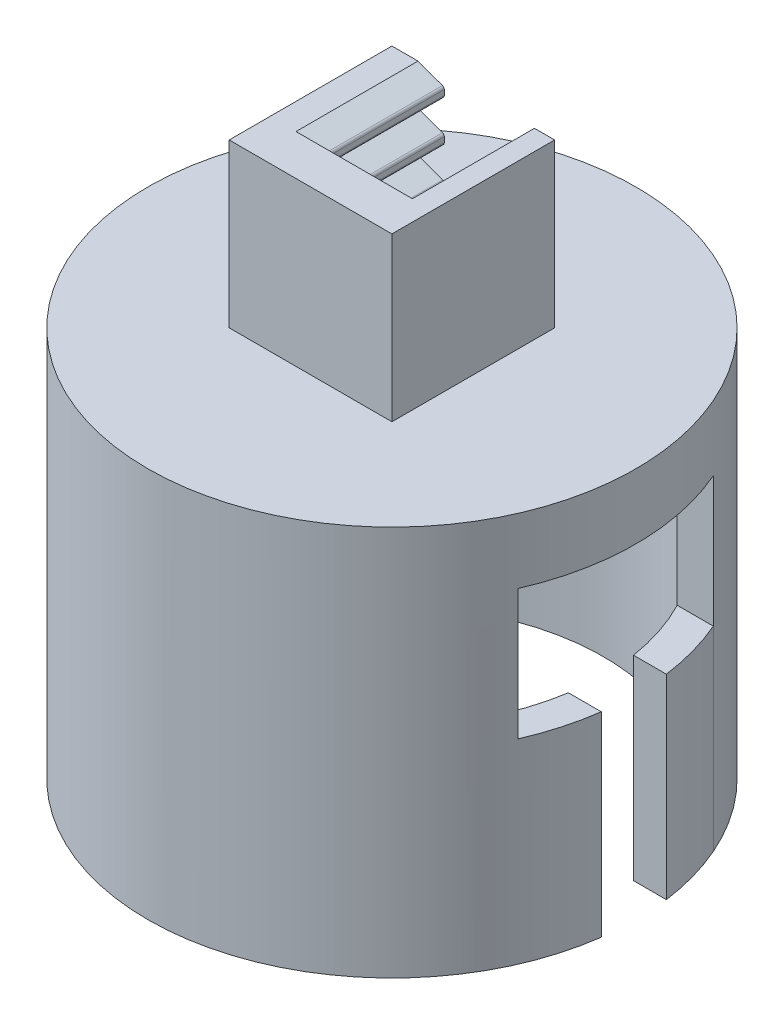
SolidWorks part; units mm, degrees
ref_plane "Front Plane" through (0, 0, 0) normal (0, 0, 1) x (1, 0, 0)
ref_plane "Top Plane" through (0, 0, 0) normal (0, 1, 0) x (1, 0, 0)
ref_plane "Right Plane" through (0, 0, 0) normal (1, 0, 0) x (0, 0, -1)
sketch "Sketch1" plane through (0, 0, 0) normal (0, 1, 0) x (1, 0, 0)
  circle A0 centre (0, 0) radius 15
  circle A1 centre (0, 0) radius 13
  dimension "D1" = 26
  dimension "D2" = 30
extrude "Boss-Extrude1" add sketch "Sketch1" along normal blind 20
sketch "Sketch2" plane through (0, 20, 0) normal (0, 1, 0) x (1, 0, 0)
  circle A0 centre (0, 0) radius 15
extrude "Boss-Extrude2" add sketch "Sketch2" along normal blind 4
ref_plane "Plane1" through (15, 0, 0) normal (1, 0, 0) x (0, 0, -1)
sketch "Sketch3" plane through (15, 0, 0) normal (1, 0, 0) x (0, 0, -1)
  line L0 (-15, 0) -> (15, 0) construction
  line L1 (-6, 12) -> (-2, 12)
  line L2 (-6, 12) -> (-6, 20)
  line L3 (-6, 20) -> (6, 20)
  line L4 (6, 12) -> (6, 20)
  line L5 (0, 24) -> (0, 0) construction
  line L6 (15, 24) -> (-15, 24) construction
  line L8 (-2, 12) -> (-2, 0)
  line L9 (-2, 0) -> (2, 0)
  line L10 (2, 12) -> (2, 0)
  line L11 (2, 12) -> (6, 12)
  dimension "D1" = 12
  dimension "D2" = 8
  dimension "D3" = 4
  dimension "D4" = 4
extrude "Cut-Extrude1" cut sketch "Sketch3" against normal blind 4
sketch "Sketch4" plane through (0, 24, 0) normal (0, 1, 0) x (1, 0, 0)
  line L0 (0, 5) -> (0, -5) construction
  line L1 (-5, 5) -> (5, 5)
  line L2 (-5, 5) -> (-5, -5)
  line L3 (-5, -5) -> (5, -5)
  line L4 (5, 5) -> (5, -5)
  line L5 (-5, 0) -> (5, 0) construction
  dimension "D1" = 10
  dimension "D2" = 10
extrude "Boss-Extrude3" add sketch "Sketch4" along normal blind 10
sketch "Sketch6" plane through (0, 0, -5) normal (0, 0, -1) x (-1, 0, 0)
  line L1 (-5, 34) -> (5, 34) construction
  line L3 (-3.7584, 34) -> (3.3958, 34)
  line L4 (-3.7584, 24) -> (3.5416, 24)
  line L405 (2.1355, 274) -> (0.2416, 274)
  line L406 (0.2416, 274) -> (0.2416, 34)
  line L407 (0.2416, 34) -> (-1.7584, 34)
  line L408 (-1.7584, 34) -> (-1.7584, 274)
  line L409 (-1.7584, 274) -> (-3.7584, 274)
  line L410 (-3.7584, 274) -> (-3.7584, 24)
  line L411 (-3.7584, 24) -> (3.5416, 24)
  line L412 (3.5416, 24) -> (3.5416, 24.6743)
  line L413 (3.5416, 24.6743) -> (1.8918, 25.2748)
  line L414 (1.7816, 25.432) -> (1.7816, 25.7555)
  line L415 (1.8918, 25.9128) -> (3.5416, 26.5133)
  line L416 (3.5416, 26.5133) -> (3.5416, 27.1876)
  line L417 (3.5416, 27.1876) -> (1.8918, 27.7881)
  line L418 (1.7816, 27.9453) -> (1.7816, 28.2688)
  line L419 (1.8918, 28.426) -> (3.5416, 29.0265)
  line L420 (3.5416, 29.0265) -> (3.5416, 29.7008)
  line L421 (3.5416, 29.7008) -> (1.8918, 30.3013)
  line L422 (1.7816, 30.4586) -> (1.7816, 30.7821)
  line L423 (1.8918, 30.9393) -> (3.5416, 31.5398)
  line L424 (3.5416, 31.5398) -> (3.5416, 32.2141)
  line L425 (3.5416, 32.2141) -> (1.8918, 32.8146)
  line L426 (1.7816, 32.9719) -> (1.7816, 33.2953)
  line L427 (1.8918, 33.4526) -> (3.5416, 34.0531)
  line L428 (3.5416, 34.0531) -> (3.5416, 34.7274)
  line L429 (3.5416, 34.7274) -> (1.8918, 35.3279)
  line L430 (1.7816, 35.4851) -> (1.7816, 35.8086)
  line L431 (1.8918, 35.9658) -> (3.5416, 36.5664)
  line L432 (3.5416, 36.5664) -> (3.5416, 37.2406)
  line L433 (3.5416, 37.2406) -> (1.8918, 37.8412)
  line L434 (1.7816, 37.9984) -> (1.7816, 38.3219)
  line L435 (1.8918, 38.4791) -> (3.5416, 39.0796)
  line L436 (3.5416, 39.0796) -> (3.5416, 39.7539)
  line L437 (3.5416, 39.7539) -> (1.8918, 40.3544)
  line L438 (1.7816, 40.5117) -> (1.7816, 40.8351)
  line L439 (1.8918, 40.9924) -> (3.5416, 41.5929)
  line L440 (3.5416, 41.5929) -> (3.5416, 42.2672)
  line L441 (3.5416, 42.2672) -> (1.8918, 42.8677)
  line L442 (1.7816, 43.025) -> (1.7816, 43.3484)
  line L443 (1.8918, 43.5057) -> (3.5416, 44.1062)
  line L444 (3.5416, 44.1062) -> (3.5416, 44.7805)
  line L445 (3.5416, 44.7805) -> (1.8918, 45.381)
  line L446 (1.7816, 45.5382) -> (1.7816, 45.8617)
  line L447 (1.8918, 46.0189) -> (3.5416, 46.6194)
  line L448 (3.5416, 46.6194) -> (3.5416, 47.2937)
  line L449 (3.5416, 47.2937) -> (1.8918, 47.8942)
  line L450 (1.7816, 48.0515) -> (1.7816, 48.375)
  line L451 (1.8918, 48.5322) -> (3.5416, 49.1327)
  line L452 (3.5416, 49.1327) -> (3.5416, 49.807)
  line L453 (3.5416, 49.807) -> (1.8918, 50.4075)
  line L454 (1.7816, 50.5648) -> (1.7816, 50.8882)
  line L455 (1.8918, 51.0455) -> (3.5416, 51.646)
  line L456 (3.5416, 51.646) -> (3.5416, 52.3203)
  line L457 (3.5416, 52.3203) -> (1.8918, 52.9208)
  line L458 (1.7816, 53.078) -> (1.7816, 53.4015)
  line L459 (1.8918, 53.5588) -> (3.5416, 54.1593)
  line L460 (3.5416, 54.1593) -> (3.5416, 54.8335)
  line L461 (3.5416, 54.8335) -> (1.8918, 55.4341)
  line L462 (1.7816, 55.5913) -> (1.7816, 55.9148)
  line L463 (1.8918, 56.072) -> (3.5416, 56.6725)
  line L464 (3.5416, 56.6725) -> (3.5416, 57.3468)
  line L465 (3.5416, 57.3468) -> (1.8918, 57.9473)
  line L466 (1.7816, 58.1046) -> (1.7816, 58.428)
  line L467 (1.8918, 58.5853) -> (3.5416, 59.1858)
  line L468 (3.5416, 59.1858) -> (3.5416, 59.8601)
  line L469 (3.5416, 59.8601) -> (1.8918, 60.4606)
  line L470 (1.7816, 60.6179) -> (1.7816, 60.9413)
  line L471 (1.8918, 61.0986) -> (3.5416, 61.6991)
  line L472 (3.5416, 61.6991) -> (3.5416, 62.3734)
  line L473 (3.5416, 62.3734) -> (1.8918, 62.9739)
  line L474 (1.7816, 63.1311) -> (1.7816, 63.4546)
  line L475 (1.8918, 63.6118) -> (3.5416, 64.2124)
  line L476 (3.5416, 64.2124) -> (3.5416, 64.8866)
  line L477 (3.5416, 64.8866) -> (1.8918, 65.4871)
  line L478 (1.7816, 65.6444) -> (1.7816, 65.9679)
  line L479 (1.8918, 66.1251) -> (3.5416, 66.7256)
  line L480 (3.5416, 66.7256) -> (3.5416, 67.3999)
  line L481 (3.5416, 67.3999) -> (1.8918, 68.0004)
  line L482 (1.7816, 68.1577) -> (1.7816, 68.4811)
  line L483 (1.8918, 68.6384) -> (3.5416, 69.2389)
  line L484 (3.5416, 69.2389) -> (3.5416, 69.9132)
  line L485 (3.5416, 69.9132) -> (1.8918, 70.5137)
  line L486 (1.7816, 70.6709) -> (1.7816, 70.9944)
  line L487 (1.8918, 71.1517) -> (3.5416, 71.7522)
  line L488 (3.5416, 71.7522) -> (3.5416, 72.4265)
  line L489 (3.5416, 72.4265) -> (1.8918, 73.027)
  line L490 (1.7816, 73.1842) -> (1.7816, 73.5077)
  line L491 (1.8918, 73.6649) -> (3.5416, 74.2654)
  line L492 (3.5416, 74.2654) -> (3.5416, 74.9397)
  line L493 (3.5416, 74.9397) -> (1.8918, 75.5402)
  line L494 (1.7816, 75.6975) -> (1.7816, 76.0209)
  line L495 (1.8918, 76.1782) -> (3.5416, 76.7787)
  line L496 (3.5416, 76.7787) -> (3.5416, 77.453)
  line L497 (3.5416, 77.453) -> (1.8918, 78.0535)
  line L498 (1.7816, 78.2108) -> (1.7816, 78.5342)
  line L499 (1.8918, 78.6915) -> (3.5416, 79.292)
  line L500 (3.5416, 79.292) -> (3.5416, 79.9663)
  line L501 (3.5416, 79.9663) -> (1.8918, 80.5668)
  line L502 (1.7816, 80.724) -> (1.7816, 81.0475)
  line L503 (1.8918, 81.2047) -> (3.5416, 81.8053)
  line L504 (3.5416, 81.8053) -> (3.5416, 82.4795)
  line L505 (3.5416, 82.4795) -> (1.8918, 83.0801)
  line L506 (1.7816, 83.2373) -> (1.7816, 83.5608)
  line L507 (1.8918, 83.718) -> (3.5416, 84.3185)
  line L508 (3.5416, 84.3185) -> (3.5416, 84.9928)
  line L509 (3.5416, 84.9928) -> (1.8918, 85.5933)
  line L510 (1.7816, 85.7506) -> (1.7816, 86.074)
  line L511 (1.8918, 86.2313) -> (3.5416, 86.8318)
  line L512 (3.5416, 86.8318) -> (3.5416, 87.5061)
  line L513 (3.5416, 87.5061) -> (1.8918, 88.1066)
  line L514 (1.7816, 88.2638) -> (1.7816, 88.5873)
  line L515 (1.8918, 88.7446) -> (3.5416, 89.3451)
  line L516 (3.5416, 89.3451) -> (3.5416, 90.0194)
  line L517 (3.5416, 90.0194) -> (1.8918, 90.6199)
  line L518 (1.7816, 90.7771) -> (1.7816, 91.1006)
  line L519 (1.8918, 91.2578) -> (3.5416, 91.8583)
  line L520 (3.5416, 91.8583) -> (3.5416, 92.5326)
  line L521 (3.5416, 92.5326) -> (1.8918, 93.1331)
  line L522 (1.7816, 93.2904) -> (1.7816, 93.6139)
  line L523 (1.8918, 93.7711) -> (3.5416, 94.3716)
  line L524 (3.5416, 94.3716) -> (3.5416, 95.0459)
  line L525 (3.5416, 95.0459) -> (1.8918, 95.6464)
  line L526 (1.7816, 95.8037) -> (1.7816, 96.1271)
  line L527 (1.8918, 96.2844) -> (3.5416, 96.8849)
  line L528 (3.5416, 96.8849) -> (3.5416, 97.5592)
  line L529 (3.5416, 97.5592) -> (1.8918, 98.1597)
  line L530 (1.7816, 98.3169) -> (1.7816, 98.6404)
  line L531 (1.8918, 98.7976) -> (3.5416, 99.3982)
  line L532 (3.5416, 99.3982) -> (3.5416, 100.0724)
  line L533 (3.5416, 100.0724) -> (1.8918, 100.673)
  line L534 (1.7816, 100.8302) -> (1.7816, 101.1537)
  line L535 (1.8918, 101.3109) -> (3.5416, 101.9114)
  line L536 (3.5416, 101.9114) -> (3.5416, 102.5857)
  line L537 (3.5416, 102.5857) -> (1.8918, 103.1862)
  line L538 (1.7816, 103.3435) -> (1.7816, 103.6669)
  line L539 (1.8918, 103.8242) -> (3.5416, 104.4247)
  line L540 (3.5416, 104.4247) -> (3.5416, 105.099)
  line L541 (3.5416, 105.099) -> (1.8918, 105.6995)
  line L542 (1.7816, 105.8568) -> (1.7816, 106.1802)
  line L543 (1.8918, 106.3375) -> (3.5416, 106.938)
  line L544 (3.5416, 106.938) -> (3.5416, 107.6123)
  line L545 (3.5416, 107.6123) -> (1.8918, 108.2128)
  line L546 (1.7816, 108.37) -> (1.7816, 108.6935)
  line L547 (1.8918, 108.8507) -> (3.5416, 109.4512)
  line L548 (3.5416, 109.4512) -> (3.5416, 110.1255)
  line L549 (3.5416, 110.1255) -> (1.8918, 110.726)
  line L550 (1.7816, 110.8833) -> (1.7816, 111.2068)
  line L551 (1.8918, 111.364) -> (3.5416, 111.9645)
  line L552 (3.5416, 111.9645) -> (3.5416, 112.6388)
  line L553 (3.5416, 112.6388) -> (1.8918, 113.2393)
  line L554 (1.7816, 113.3966) -> (1.7816, 113.72)
  line L555 (1.8918, 113.8773) -> (3.5416, 114.4778)
  line L556 (3.5416, 114.4778) -> (3.5416, 115.1521)
  line L557 (3.5416, 115.1521) -> (1.8918, 115.7526)
  line L558 (1.7816, 115.9098) -> (1.7816, 116.2333)
  line L559 (1.8918, 116.3906) -> (3.5416, 116.9911)
  line L560 (3.5416, 116.9911) -> (3.5416, 117.6653)
  line L561 (3.5416, 117.6653) -> (1.8918, 118.2659)
  line L562 (1.7816, 118.4231) -> (1.7816, 118.7466)
  line L563 (1.8918, 118.9038) -> (3.5416, 119.5043)
  line L564 (3.5416, 119.5043) -> (3.5416, 120.1786)
  line L565 (3.5416, 120.1786) -> (1.8918, 120.7791)
  line L566 (1.7816, 120.9364) -> (1.7816, 121.2598)
  line L567 (1.8918, 121.4171) -> (3.5416, 122.0176)
  line L568 (3.5416, 122.0176) -> (3.5416, 122.6919)
  line L569 (3.5416, 122.6919) -> (1.8918, 123.2924)
  line L570 (1.7816, 123.4497) -> (1.7816, 123.7731)
  line L571 (1.8918, 123.9304) -> (3.5416, 124.5309)
  line L572 (3.5416, 124.5309) -> (3.5416, 125.2052)
  line L573 (3.5416, 125.2052) -> (1.8918, 125.8057)
  line L574 (1.7816, 125.9629) -> (1.7816, 126.2864)
  line L575 (1.8918, 126.4436) -> (3.5416, 127.0442)
  line L576 (3.5416, 127.0442) -> (3.5416, 127.7184)
  line L577 (3.5416, 127.7184) -> (1.8918, 128.3189)
  line L578 (1.7816, 128.4762) -> (1.7816, 128.7997)
  line L579 (1.8918, 128.9569) -> (3.5416, 129.5574)
  line L580 (3.5416, 129.5574) -> (3.5416, 130.2317)
  line L581 (3.5416, 130.2317) -> (1.8918, 130.8322)
  line L582 (1.7816, 130.9895) -> (1.7816, 131.3129)
  line L583 (1.8918, 131.4702) -> (3.5416, 132.0707)
  line L584 (3.5416, 132.0707) -> (3.5416, 132.745)
  line L585 (3.5416, 132.745) -> (1.8918, 133.3455)
  line L586 (1.7816, 133.5027) -> (1.7816, 133.8262)
  line L587 (1.8918, 133.9835) -> (3.5416, 134.584)
  line L588 (3.5416, 134.584) -> (3.5416, 135.2583)
  line L589 (3.5416, 135.2583) -> (1.8918, 135.8588)
  line L590 (1.7816, 136.016) -> (1.7816, 136.3395)
  line L591 (1.8918, 136.4967) -> (3.5416, 137.0972)
  line L592 (3.5416, 137.0972) -> (3.5416, 137.7715)
  line L593 (3.5416, 137.7715) -> (1.8918, 138.372)
  line L594 (1.7816, 138.5293) -> (1.7816, 138.8527)
  line L595 (1.8918, 139.01) -> (3.5416, 139.6105)
  line L596 (3.5416, 139.6105) -> (3.5416, 140.2848)
  line L597 (3.5416, 140.2848) -> (1.8918, 140.8853)
  line L598 (1.7816, 141.0426) -> (1.7816, 141.366)
  line L599 (1.8918, 141.5233) -> (3.5416, 142.1238)
  line L600 (3.5416, 142.1238) -> (3.5416, 142.7981)
  line L601 (3.5416, 142.7981) -> (1.8918, 143.3986)
  line L602 (1.7816, 143.5558) -> (1.7816, 143.8793)
  line L603 (1.8918, 144.0365) -> (3.5416, 144.6371)
  line L604 (3.5416, 144.6371) -> (3.5416, 145.3113)
  line L605 (3.5416, 145.3113) -> (1.8918, 145.9119)
  line L606 (1.7816, 146.0691) -> (1.7816, 146.3926)
  line L607 (1.8918, 146.5498) -> (3.5416, 147.1503)
  line L608 (3.5416, 147.1503) -> (3.5416, 147.8246)
  line L609 (3.5416, 147.8246) -> (1.8918, 148.4251)
  line L610 (1.7816, 148.5824) -> (1.7816, 148.9058)
  line L611 (1.8918, 149.0631) -> (3.5416, 149.6636)
  line L612 (3.5416, 149.6636) -> (3.5416, 150.3379)
  line L613 (3.5416, 150.3379) -> (1.8918, 150.9384)
  line L614 (1.7816, 151.0956) -> (1.7816, 151.4191)
  line L615 (1.8918, 151.5764) -> (3.5416, 152.1769)
  line L616 (3.5416, 152.1769) -> (3.5416, 152.8512)
  line L617 (3.5416, 152.8512) -> (1.8918, 153.4517)
  line L618 (1.7816, 153.6089) -> (1.7816, 153.9324)
  line L619 (1.8918, 154.0896) -> (3.5416, 154.6901)
  line L620 (3.5416, 154.6901) -> (3.5416, 155.3644)
  line L621 (3.5416, 155.3644) -> (1.8918, 155.9649)
  line L622 (1.7816, 156.1222) -> (1.7816, 156.4457)
  line L623 (1.8918, 156.6029) -> (3.5416, 157.2034)
  line L624 (3.5416, 157.2034) -> (3.5416, 157.8777)
  line L625 (3.5416, 157.8777) -> (1.8918, 158.4782)
  line L626 (1.7816, 158.6355) -> (1.7816, 158.9589)
  line L627 (1.8918, 159.1162) -> (3.5416, 159.7167)
  line L628 (3.5416, 159.7167) -> (3.5416, 160.391)
  line L629 (3.5416, 160.391) -> (1.8918, 160.9915)
  line L630 (1.7816, 161.1487) -> (1.7816, 161.4722)
  line L631 (1.8918, 161.6294) -> (3.5416, 162.23)
  line L632 (3.5416, 162.23) -> (3.5416, 162.9042)
  line L633 (3.5416, 162.9042) -> (1.8918, 163.5048)
  line L634 (1.7816, 163.662) -> (1.7816, 163.9855)
  line L635 (1.8918, 164.1427) -> (3.5416, 164.7432)
  line L636 (3.5416, 164.7432) -> (3.5416, 165.4175)
  line L637 (3.5416, 165.4175) -> (1.8918, 166.018)
  line L638 (1.7816, 166.1753) -> (1.7816, 166.4987)
  line L639 (1.8918, 166.656) -> (3.5416, 167.2565)
  line L640 (3.5416, 167.2565) -> (3.5416, 167.9308)
  line L641 (3.5416, 167.9308) -> (1.8918, 168.5313)
  line L642 (1.7816, 168.6886) -> (1.7816, 169.012)
  line L643 (1.8918, 169.1693) -> (3.5416, 169.7698)
  line L644 (3.5416, 169.7698) -> (3.5416, 170.4441)
  line L645 (3.5416, 170.4441) -> (1.8918, 171.0446)
  line L646 (1.7816, 171.2018) -> (1.7816, 171.5253)
  line L647 (1.8918, 171.6825) -> (3.5416, 172.283)
  line L648 (3.5416, 172.283) -> (3.5416, 172.9573)
  line L649 (3.5416, 172.9573) -> (1.8918, 173.5578)
  line L650 (1.7816, 173.7151) -> (1.7816, 174.0386)
  line L651 (1.8918, 174.1958) -> (3.5416, 174.7963)
  line L652 (3.5416, 174.7963) -> (3.5416, 175.4706)
  line L653 (3.5416, 175.4706) -> (1.8918, 176.0711)
  line L654 (1.7816, 176.2284) -> (1.7816, 176.5518)
  line L655 (1.8918, 176.7091) -> (3.5416, 177.3096)
  line L656 (3.5416, 177.3096) -> (3.5416, 177.9839)
  line L657 (3.5416, 177.9839) -> (1.8918, 178.5844)
  line L658 (1.7816, 178.7416) -> (1.7816, 179.0651)
  line L659 (1.8918, 179.2224) -> (3.5416, 179.8229)
  line L660 (3.5416, 179.8229) -> (3.5416, 180.4971)
  line L661 (3.5416, 180.4971) -> (1.8918, 181.0977)
  line L662 (1.7816, 181.2549) -> (1.7816, 181.5784)
  line L663 (1.8918, 181.7356) -> (3.5416, 182.3361)
  line L664 (3.5416, 182.3361) -> (3.5416, 183.0104)
  line L665 (3.5416, 183.0104) -> (1.8918, 183.6109)
  line L666 (1.7816, 183.7682) -> (1.7816, 184.0916)
  line L667 (1.8918, 184.2489) -> (3.5416, 184.8494)
  line L668 (3.5416, 184.8494) -> (3.5416, 185.5237)
  line L669 (3.5416, 185.5237) -> (1.8918, 186.1242)
  line L670 (1.7816, 186.2815) -> (1.7816, 186.6049)
  line L671 (1.8918, 186.7622) -> (3.5416, 187.3627)
  line L672 (3.5416, 187.3627) -> (3.5416, 188.037)
  line L673 (3.5416, 188.037) -> (1.8918, 188.6375)
  line L674 (1.7816, 188.7947) -> (1.7816, 189.1182)
  line L675 (1.8918, 189.2754) -> (3.5416, 189.876)
  line L676 (3.5416, 189.876) -> (3.5416, 190.5502)
  line L677 (3.5416, 190.5502) -> (1.8918, 191.1507)
  line L678 (1.7816, 191.308) -> (1.7816, 191.6315)
  line L679 (1.8918, 191.7887) -> (3.5416, 192.3892)
  line L680 (3.5416, 192.3892) -> (3.5416, 193.0635)
  line L681 (3.5416, 193.0635) -> (1.8918, 193.664)
  line L682 (1.7816, 193.8213) -> (1.7816, 194.1447)
  line L683 (1.8918, 194.302) -> (3.5416, 194.9025)
  line L684 (3.5416, 194.9025) -> (3.5416, 195.5768)
  line L685 (3.5416, 195.5768) -> (1.8918, 196.1773)
  line L686 (1.7816, 196.3345) -> (1.7816, 196.658)
  line L687 (1.8918, 196.8153) -> (3.5416, 197.4158)
  line L688 (3.5416, 197.4158) -> (3.5416, 198.0901)
  line L689 (3.5416, 198.0901) -> (1.8918, 198.6906)
  line L690 (1.7816, 198.8478) -> (1.7816, 199.1713)
  line L691 (1.8918, 199.3285) -> (3.5416, 199.929)
  line L692 (3.5416, 199.929) -> (3.5416, 200.6033)
  line L693 (3.5416, 200.6033) -> (1.8918, 201.2038)
  line L694 (1.7816, 201.3611) -> (1.7816, 201.6845)
  line L695 (1.8918, 201.8418) -> (3.5416, 202.4423)
  line L696 (3.5416, 202.4423) -> (3.5416, 203.1166)
  line L697 (3.5416, 203.1166) -> (1.8918, 203.7171)
  line L698 (1.7816, 203.8744) -> (1.7816, 204.1978)
  line L699 (1.8918, 204.3551) -> (3.5416, 204.9556)
  line L700 (3.5416, 204.9556) -> (3.5416, 205.6299)
  line L701 (3.5416, 205.6299) -> (1.8918, 206.2304)
  line L702 (1.7816, 206.3876) -> (1.7816, 206.7111)
  line L703 (1.8918, 206.8683) -> (3.5416, 207.4689)
  line L704 (3.5416, 207.4689) -> (3.5416, 208.1431)
  line L705 (3.5416, 208.1431) -> (1.8918, 208.7437)
  line L706 (1.7816, 208.9009) -> (1.7816, 209.2244)
  line L707 (1.8918, 209.3816) -> (3.5416, 209.9821)
  line L708 (3.5416, 209.9821) -> (3.5416, 210.6564)
  line L709 (3.5416, 210.6564) -> (1.8918, 211.2569)
  line L710 (1.7816, 211.4142) -> (1.7816, 211.7376)
  line L711 (1.8918, 211.8949) -> (3.5416, 212.4954)
  line L712 (3.5416, 212.4954) -> (3.5416, 213.1697)
  line L713 (3.5416, 213.1697) -> (1.8918, 213.7702)
  line L714 (1.7816, 213.9274) -> (1.7816, 214.2509)
  line L715 (1.8918, 214.4082) -> (3.5416, 215.0087)
  line L716 (3.5416, 215.0087) -> (3.5416, 215.683)
  line L717 (3.5416, 215.683) -> (1.8918, 216.2835)
  line L718 (1.7816, 216.4407) -> (1.7816, 216.7642)
  line L719 (1.8918, 216.9214) -> (3.5416, 217.5219)
  line L720 (3.5416, 217.5219) -> (3.5416, 218.1962)
  line L721 (3.5416, 218.1962) -> (1.8918, 218.7967)
  line L722 (1.7816, 218.954) -> (1.7816, 219.2775)
  line L723 (1.8918, 219.4347) -> (3.5416, 220.0352)
  line L724 (3.5416, 220.0352) -> (3.5416, 220.7095)
  line L725 (3.5416, 220.7095) -> (1.8918, 221.31)
  line L726 (1.7816, 221.4673) -> (1.7816, 221.7907)
  line L727 (1.8918, 221.948) -> (3.5416, 222.5485)
  line L728 (3.5416, 222.5485) -> (3.5416, 223.2228)
  line L729 (3.5416, 223.2228) -> (1.8918, 223.8233)
  line L730 (1.7816, 223.9805) -> (1.7816, 224.304)
  line L731 (1.8918, 224.4612) -> (3.5416, 225.0618)
  line L732 (3.5416, 225.0618) -> (3.5416, 225.736)
  line L733 (3.5416, 225.736) -> (1.8918, 226.3366)
  line L734 (1.7816, 226.4938) -> (1.7816, 226.8173)
  line L735 (1.8918, 226.9745) -> (3.5416, 227.575)
  line L736 (3.5416, 227.575) -> (3.5416, 228.2493)
  line L737 (3.5416, 228.2493) -> (1.8918, 228.8498)
  line L738 (1.7816, 229.0071) -> (1.7816, 229.3305)
  line L739 (1.8918, 229.4878) -> (3.5416, 230.0883)
  line L740 (3.5416, 230.0883) -> (3.5416, 230.7626)
  line L741 (3.5416, 230.7626) -> (1.8918, 231.3631)
  line L742 (1.7816, 231.5204) -> (1.7816, 231.8438)
  line L743 (1.8918, 232.0011) -> (3.5416, 232.6016)
  line L744 (3.5416, 232.6016) -> (3.5416, 233.2759)
  line L745 (3.5416, 233.2759) -> (1.8918, 233.8764)
  line L746 (1.7816, 234.0336) -> (1.7816, 234.3571)
  line L747 (1.8918, 234.5143) -> (3.5416, 235.1148)
  line L748 (3.5416, 235.1148) -> (3.5416, 235.7891)
  line L749 (3.5416, 235.7891) -> (1.8918, 236.3896)
  line L750 (1.7816, 236.5469) -> (1.7816, 236.8704)
  line L751 (1.8918, 237.0276) -> (3.5416, 237.6281)
  line L752 (3.5416, 237.6281) -> (3.5416, 238.3024)
  line L753 (3.5416, 238.3024) -> (1.8918, 238.9029)
  line L754 (1.7816, 239.0602) -> (1.7816, 239.3836)
  line L755 (1.8918, 239.5409) -> (3.5416, 240.1414)
  line L756 (3.5416, 240.1414) -> (3.5416, 240.8157)
  line L757 (3.5416, 240.8157) -> (1.8918, 241.4162)
  line L758 (1.7816, 241.5734) -> (1.7816, 241.8969)
  line L759 (1.8918, 242.0542) -> (3.5416, 242.6547)
  line L760 (3.5416, 242.6547) -> (3.5416, 243.3289)
  line L761 (3.5416, 243.3289) -> (1.8918, 243.9295)
  line L762 (1.7816, 244.0867) -> (1.7816, 244.4102)
  line L763 (1.8918, 244.5674) -> (3.5416, 245.1679)
  line L764 (3.5416, 245.1679) -> (3.5416, 245.8422)
  line L765 (3.5416, 245.8422) -> (1.8918, 246.4427)
  line L766 (1.7816, 246.6) -> (1.7816, 246.9234)
  line L767 (1.8918, 247.0807) -> (3.5416, 247.6812)
  line L768 (3.5416, 247.6812) -> (3.5416, 248.3555)
  line L769 (3.5416, 248.3555) -> (1.8918, 248.956)
  line L770 (1.7816, 249.1133) -> (1.7816, 249.4367)
  line L771 (1.8918, 249.594) -> (3.5416, 250.1945)
  line L772 (3.5416, 250.1945) -> (3.5416, 250.8688)
  line L773 (3.5416, 250.8688) -> (1.8918, 251.4693)
  line L774 (1.7816, 251.6265) -> (1.7816, 251.95)
  line L775 (1.8918, 252.1072) -> (3.5416, 252.7078)
  line L776 (3.5416, 252.7078) -> (3.5416, 253.382)
  line L777 (3.5416, 253.382) -> (1.8918, 253.9825)
  line L778 (1.7816, 254.1398) -> (1.7816, 254.4633)
  line L779 (1.8918, 254.6205) -> (3.5416, 255.221)
  line L780 (3.5416, 255.221) -> (3.5416, 255.8953)
  line L781 (3.5416, 255.8953) -> (1.8918, 256.4958)
  line L782 (1.7816, 256.6531) -> (1.7816, 256.9765)
  line L783 (1.8918, 257.1338) -> (3.5416, 257.7343)
  line L784 (3.5416, 257.7343) -> (3.5416, 258.4086)
  line L785 (3.5416, 258.4086) -> (1.8918, 259.0091)
  line L786 (1.7816, 259.1663) -> (1.7816, 259.4898)
  line L787 (1.8918, 259.6471) -> (3.5416, 260.2476)
  line L788 (3.5416, 260.2476) -> (3.5416, 260.9219)
  line L789 (3.5416, 260.9219) -> (1.8918, 261.5224)
  line L790 (1.7816, 261.6796) -> (1.7816, 262.0031)
  line L791 (1.8918, 262.1603) -> (3.5416, 262.7608)
  line L792 (3.5416, 262.7608) -> (3.5416, 263.4351)
  line L793 (3.5416, 263.4351) -> (1.8918, 264.0356)
  line L794 (1.7816, 264.1929) -> (1.7816, 264.5163)
  line L795 (1.8918, 264.6736) -> (3.5416, 265.2741)
  line L796 (3.5416, 265.2741) -> (3.5416, 265.9484)
  line L797 (3.5416, 265.9484) -> (1.8918, 266.5489)
  line L798 (1.7816, 266.7062) -> (1.7816, 267.0296)
  line L799 (1.8918, 267.1869) -> (3.5416, 267.7874)
  line L800 (3.5416, 267.7874) -> (3.5416, 268.4617)
  line L801 (3.5416, 268.4617) -> (1.8918, 269.0622)
  line L802 (1.7816, 269.2194) -> (1.7816, 269.5429)
  line L803 (1.8918, 269.7001) -> (3.5416, 270.3007)
  line L804 (3.5416, 270.3007) -> (3.5416, 270.9749)
  line L805 (3.5416, 270.9749) -> (1.8918, 271.5755)
  line L806 (1.7816, 271.7327) -> (1.7816, 272.0562)
  line L807 (1.8918, 272.2134) -> (3.5416, 272.8139)
  line L808 (3.5416, 272.8139) -> (3.5416, 273.4882)
  line L809 (3.5416, 273.4882) -> (2.1355, 274)
  line L815 (-3.7584, 34) -> (-3.7584, 24)
  line L816 (-3.7584, 24) -> (3.5416, 24)
  line L817 (3.5416, 24) -> (3.5416, 24.6743)
  line L818 (3.5416, 24.6743) -> (1.8918, 25.2748)
  line L819 (1.7816, 25.432) -> (1.7816, 25.7555)
  line L820 (1.8918, 25.9128) -> (3.5416, 26.5133)
  line L821 (3.5416, 26.5133) -> (3.5416, 27.1876)
  line L822 (3.5416, 27.1876) -> (1.8918, 27.7881)
  line L823 (1.7816, 27.9453) -> (1.7816, 28.2688)
  line L824 (1.8918, 28.426) -> (3.5416, 29.0265)
  line L825 (3.5416, 29.0265) -> (3.5416, 29.7008)
  line L826 (3.5416, 29.7008) -> (1.8918, 30.3013)
  line L827 (1.7816, 30.4586) -> (1.7816, 30.7821)
  line L828 (1.8918, 30.9393) -> (3.5416, 31.5398)
  line L829 (3.5416, 31.5398) -> (3.5416, 32.2141)
  line L830 (3.5416, 32.2141) -> (1.8918, 32.8146)
  line L831 (1.7816, 32.9719) -> (1.7816, 33.2953)
  line L832 (1.8918, 33.4526) -> (3.3958, 34)
  arc A198 (1.7816, 25.432) -> (1.8918, 25.2748) centre (1.949, 25.432) ccw
  arc A199 (1.8918, 25.9128) -> (1.7816, 25.7555) centre (1.949, 25.7555) ccw
  arc A200 (1.7816, 27.9453) -> (1.8918, 27.7881) centre (1.949, 27.9453) ccw
  arc A201 (1.8918, 28.426) -> (1.7816, 28.2688) centre (1.949, 28.2688) ccw
  arc A202 (1.7816, 30.4586) -> (1.8918, 30.3013) centre (1.949, 30.4586) ccw
  arc A203 (1.8918, 30.9393) -> (1.7816, 30.7821) centre (1.949, 30.7821) ccw
  arc A204 (1.7816, 32.9719) -> (1.8918, 32.8146) centre (1.949, 32.9719) ccw
  arc A205 (1.8918, 33.4526) -> (1.7816, 33.2953) centre (1.949, 33.2953) ccw
  arc A206 (1.7816, 35.4851) -> (1.8918, 35.3279) centre (1.949, 35.4851) ccw
  arc A207 (1.8918, 35.9658) -> (1.7816, 35.8086) centre (1.949, 35.8086) ccw
  arc A208 (1.7816, 37.9984) -> (1.8918, 37.8412) centre (1.949, 37.9984) ccw
  arc A209 (1.8918, 38.4791) -> (1.7816, 38.3219) centre (1.949, 38.3219) ccw
  arc A210 (1.7816, 40.5117) -> (1.8918, 40.3544) centre (1.949, 40.5117) ccw
  arc A211 (1.8918, 40.9924) -> (1.7816, 40.8351) centre (1.949, 40.8351) ccw
  arc A212 (1.7816, 43.025) -> (1.8918, 42.8677) centre (1.949, 43.025) ccw
  arc A213 (1.8918, 43.5057) -> (1.7816, 43.3484) centre (1.949, 43.3484) ccw
  arc A214 (1.7816, 45.5382) -> (1.8918, 45.381) centre (1.949, 45.5382) ccw
  arc A215 (1.8918, 46.0189) -> (1.7816, 45.8617) centre (1.949, 45.8617) ccw
  arc A216 (1.7816, 48.0515) -> (1.8918, 47.8942) centre (1.949, 48.0515) ccw
  arc A217 (1.8918, 48.5322) -> (1.7816, 48.375) centre (1.949, 48.375) ccw
  arc A218 (1.7816, 50.5648) -> (1.8918, 50.4075) centre (1.949, 50.5648) ccw
  arc A219 (1.8918, 51.0455) -> (1.7816, 50.8882) centre (1.949, 50.8882) ccw
  arc A220 (1.7816, 53.078) -> (1.8918, 52.9208) centre (1.949, 53.078) ccw
  arc A221 (1.8918, 53.5588) -> (1.7816, 53.4015) centre (1.949, 53.4015) ccw
  arc A222 (1.7816, 55.5913) -> (1.8918, 55.4341) centre (1.949, 55.5913) ccw
  arc A223 (1.8918, 56.072) -> (1.7816, 55.9148) centre (1.949, 55.9148) ccw
  arc A224 (1.7816, 58.1046) -> (1.8918, 57.9473) centre (1.949, 58.1046) ccw
  arc A225 (1.8918, 58.5853) -> (1.7816, 58.428) centre (1.949, 58.428) ccw
  arc A226 (1.7816, 60.6179) -> (1.8918, 60.4606) centre (1.949, 60.6179) ccw
  arc A227 (1.8918, 61.0986) -> (1.7816, 60.9413) centre (1.949, 60.9413) ccw
  arc A228 (1.7816, 63.1311) -> (1.8918, 62.9739) centre (1.949, 63.1311) ccw
  arc A229 (1.8918, 63.6118) -> (1.7816, 63.4546) centre (1.949, 63.4546) ccw
  arc A230 (1.7816, 65.6444) -> (1.8918, 65.4871) centre (1.949, 65.6444) ccw
  arc A231 (1.8918, 66.1251) -> (1.7816, 65.9679) centre (1.949, 65.9679) ccw
  arc A232 (1.7816, 68.1577) -> (1.8918, 68.0004) centre (1.949, 68.1577) ccw
  arc A233 (1.8918, 68.6384) -> (1.7816, 68.4811) centre (1.949, 68.4811) ccw
  arc A234 (1.7816, 70.6709) -> (1.8918, 70.5137) centre (1.949, 70.6709) ccw
  arc A235 (1.8918, 71.1517) -> (1.7816, 70.9944) centre (1.949, 70.9944) ccw
  arc A236 (1.7816, 73.1842) -> (1.8918, 73.027) centre (1.949, 73.1842) ccw
  arc A237 (1.8918, 73.6649) -> (1.7816, 73.5077) centre (1.949, 73.5077) ccw
  arc A238 (1.7816, 75.6975) -> (1.8918, 75.5402) centre (1.949, 75.6975) ccw
  arc A239 (1.8918, 76.1782) -> (1.7816, 76.0209) centre (1.949, 76.0209) ccw
  arc A240 (1.7816, 78.2108) -> (1.8918, 78.0535) centre (1.949, 78.2108) ccw
  arc A241 (1.8918, 78.6915) -> (1.7816, 78.5342) centre (1.949, 78.5342) ccw
  arc A242 (1.7816, 80.724) -> (1.8918, 80.5668) centre (1.949, 80.724) ccw
  arc A243 (1.8918, 81.2047) -> (1.7816, 81.0475) centre (1.949, 81.0475) ccw
  arc A244 (1.7816, 83.2373) -> (1.8918, 83.0801) centre (1.949, 83.2373) ccw
  arc A245 (1.8918, 83.718) -> (1.7816, 83.5608) centre (1.949, 83.5608) ccw
  arc A246 (1.7816, 85.7506) -> (1.8918, 85.5933) centre (1.949, 85.7506) ccw
  arc A247 (1.8918, 86.2313) -> (1.7816, 86.074) centre (1.949, 86.074) ccw
  arc A248 (1.7816, 88.2638) -> (1.8918, 88.1066) centre (1.949, 88.2638) ccw
  arc A249 (1.8918, 88.7446) -> (1.7816, 88.5873) centre (1.949, 88.5873) ccw
  arc A250 (1.7816, 90.7771) -> (1.8918, 90.6199) centre (1.949, 90.7771) ccw
  arc A251 (1.8918, 91.2578) -> (1.7816, 91.1006) centre (1.949, 91.1006) ccw
  arc A252 (1.7816, 93.2904) -> (1.8918, 93.1331) centre (1.949, 93.2904) ccw
  arc A253 (1.8918, 93.7711) -> (1.7816, 93.6139) centre (1.949, 93.6139) ccw
  arc A254 (1.7816, 95.8037) -> (1.8918, 95.6464) centre (1.949, 95.8037) ccw
  arc A255 (1.8918, 96.2844) -> (1.7816, 96.1271) centre (1.949, 96.1271) ccw
  arc A256 (1.7816, 98.3169) -> (1.8918, 98.1597) centre (1.949, 98.3169) ccw
  arc A257 (1.8918, 98.7976) -> (1.7816, 98.6404) centre (1.949, 98.6404) ccw
  arc A258 (1.7816, 100.8302) -> (1.8918, 100.673) centre (1.949, 100.8302) ccw
  arc A259 (1.8918, 101.3109) -> (1.7816, 101.1537) centre (1.949, 101.1537) ccw
  arc A260 (1.7816, 103.3435) -> (1.8918, 103.1862) centre (1.949, 103.3435) ccw
  arc A261 (1.8918, 103.8242) -> (1.7816, 103.6669) centre (1.949, 103.6669) ccw
  arc A262 (1.7816, 105.8568) -> (1.8918, 105.6995) centre (1.949, 105.8568) ccw
  arc A263 (1.8918, 106.3375) -> (1.7816, 106.1802) centre (1.949, 106.1802) ccw
  arc A264 (1.7816, 108.37) -> (1.8918, 108.2128) centre (1.949, 108.37) ccw
  arc A265 (1.8918, 108.8507) -> (1.7816, 108.6935) centre (1.949, 108.6935) ccw
  arc A266 (1.7816, 110.8833) -> (1.8918, 110.726) centre (1.949, 110.8833) ccw
  arc A267 (1.8918, 111.364) -> (1.7816, 111.2068) centre (1.949, 111.2068) ccw
  arc A268 (1.7816, 113.3966) -> (1.8918, 113.2393) centre (1.949, 113.3966) ccw
  arc A269 (1.8918, 113.8773) -> (1.7816, 113.72) centre (1.949, 113.72) ccw
  arc A270 (1.7816, 115.9098) -> (1.8918, 115.7526) centre (1.949, 115.9098) ccw
  arc A271 (1.8918, 116.3906) -> (1.7816, 116.2333) centre (1.949, 116.2333) ccw
  arc A272 (1.7816, 118.4231) -> (1.8918, 118.2659) centre (1.949, 118.4231) ccw
  arc A273 (1.8918, 118.9038) -> (1.7816, 118.7466) centre (1.949, 118.7466) ccw
  arc A274 (1.7816, 120.9364) -> (1.8918, 120.7791) centre (1.949, 120.9364) ccw
  arc A275 (1.8918, 121.4171) -> (1.7816, 121.2598) centre (1.949, 121.2598) ccw
  arc A276 (1.7816, 123.4497) -> (1.8918, 123.2924) centre (1.949, 123.4497) ccw
  arc A277 (1.8918, 123.9304) -> (1.7816, 123.7731) centre (1.949, 123.7731) ccw
  arc A278 (1.7816, 125.9629) -> (1.8918, 125.8057) centre (1.949, 125.9629) ccw
  arc A279 (1.8918, 126.4436) -> (1.7816, 126.2864) centre (1.949, 126.2864) ccw
  arc A280 (1.7816, 128.4762) -> (1.8918, 128.3189) centre (1.949, 128.4762) ccw
  arc A281 (1.8918, 128.9569) -> (1.7816, 128.7997) centre (1.949, 128.7997) ccw
  arc A282 (1.7816, 130.9895) -> (1.8918, 130.8322) centre (1.949, 130.9895) ccw
  arc A283 (1.8918, 131.4702) -> (1.7816, 131.3129) centre (1.949, 131.3129) ccw
  arc A284 (1.7816, 133.5027) -> (1.8918, 133.3455) centre (1.949, 133.5027) ccw
  arc A285 (1.8918, 133.9835) -> (1.7816, 133.8262) centre (1.949, 133.8262) ccw
  arc A286 (1.7816, 136.016) -> (1.8918, 135.8588) centre (1.949, 136.016) ccw
  arc A287 (1.8918, 136.4967) -> (1.7816, 136.3395) centre (1.949, 136.3395) ccw
  arc A288 (1.7816, 138.5293) -> (1.8918, 138.372) centre (1.949, 138.5293) ccw
  arc A289 (1.8918, 139.01) -> (1.7816, 138.8527) centre (1.949, 138.8527) ccw
  arc A290 (1.7816, 141.0426) -> (1.8918, 140.8853) centre (1.949, 141.0426) ccw
  arc A291 (1.8918, 141.5233) -> (1.7816, 141.366) centre (1.949, 141.366) ccw
  arc A292 (1.7816, 143.5558) -> (1.8918, 143.3986) centre (1.949, 143.5558) ccw
  arc A293 (1.8918, 144.0365) -> (1.7816, 143.8793) centre (1.949, 143.8793) ccw
  arc A294 (1.7816, 146.0691) -> (1.8918, 145.9119) centre (1.949, 146.0691) ccw
  arc A295 (1.8918, 146.5498) -> (1.7816, 146.3926) centre (1.949, 146.3926) ccw
  arc A296 (1.7816, 148.5824) -> (1.8918, 148.4251) centre (1.949, 148.5824) ccw
  arc A297 (1.8918, 149.0631) -> (1.7816, 148.9058) centre (1.949, 148.9058) ccw
  arc A298 (1.7816, 151.0956) -> (1.8918, 150.9384) centre (1.949, 151.0956) ccw
  arc A299 (1.8918, 151.5764) -> (1.7816, 151.4191) centre (1.949, 151.4191) ccw
  arc A300 (1.7816, 153.6089) -> (1.8918, 153.4517) centre (1.949, 153.6089) ccw
  arc A301 (1.8918, 154.0896) -> (1.7816, 153.9324) centre (1.949, 153.9324) ccw
  arc A302 (1.7816, 156.1222) -> (1.8918, 155.9649) centre (1.949, 156.1222) ccw
  arc A303 (1.8918, 156.6029) -> (1.7816, 156.4457) centre (1.949, 156.4457) ccw
  arc A304 (1.7816, 158.6355) -> (1.8918, 158.4782) centre (1.949, 158.6355) ccw
  arc A305 (1.8918, 159.1162) -> (1.7816, 158.9589) centre (1.949, 158.9589) ccw
  arc A306 (1.7816, 161.1487) -> (1.8918, 160.9915) centre (1.949, 161.1487) ccw
  arc A307 (1.8918, 161.6294) -> (1.7816, 161.4722) centre (1.949, 161.4722) ccw
  arc A308 (1.7816, 163.662) -> (1.8918, 163.5048) centre (1.949, 163.662) ccw
  arc A309 (1.8918, 164.1427) -> (1.7816, 163.9855) centre (1.949, 163.9855) ccw
  arc A310 (1.7816, 166.1753) -> (1.8918, 166.018) centre (1.949, 166.1753) ccw
  arc A311 (1.8918, 166.656) -> (1.7816, 166.4987) centre (1.949, 166.4987) ccw
  arc A312 (1.7816, 168.6886) -> (1.8918, 168.5313) centre (1.949, 168.6886) ccw
  arc A313 (1.8918, 169.1693) -> (1.7816, 169.012) centre (1.949, 169.012) ccw
  arc A314 (1.7816, 171.2018) -> (1.8918, 171.0446) centre (1.949, 171.2018) ccw
  arc A315 (1.8918, 171.6825) -> (1.7816, 171.5253) centre (1.949, 171.5253) ccw
  arc A316 (1.7816, 173.7151) -> (1.8918, 173.5578) centre (1.949, 173.7151) ccw
  arc A317 (1.8918, 174.1958) -> (1.7816, 174.0386) centre (1.949, 174.0386) ccw
  arc A318 (1.7816, 176.2284) -> (1.8918, 176.0711) centre (1.949, 176.2284) ccw
  arc A319 (1.8918, 176.7091) -> (1.7816, 176.5518) centre (1.949, 176.5518) ccw
  arc A320 (1.7816, 178.7416) -> (1.8918, 178.5844) centre (1.949, 178.7416) ccw
  arc A321 (1.8918, 179.2224) -> (1.7816, 179.0651) centre (1.949, 179.0651) ccw
  arc A322 (1.7816, 181.2549) -> (1.8918, 181.0977) centre (1.949, 181.2549) ccw
  arc A323 (1.8918, 181.7356) -> (1.7816, 181.5784) centre (1.949, 181.5784) ccw
  arc A324 (1.7816, 183.7682) -> (1.8918, 183.6109) centre (1.949, 183.7682) ccw
  arc A325 (1.8918, 184.2489) -> (1.7816, 184.0916) centre (1.949, 184.0916) ccw
  arc A326 (1.7816, 186.2815) -> (1.8918, 186.1242) centre (1.949, 186.2815) ccw
  arc A327 (1.8918, 186.7622) -> (1.7816, 186.6049) centre (1.949, 186.6049) ccw
  arc A328 (1.7816, 188.7947) -> (1.8918, 188.6375) centre (1.949, 188.7947) ccw
  arc A329 (1.8918, 189.2754) -> (1.7816, 189.1182) centre (1.949, 189.1182) ccw
  arc A330 (1.7816, 191.308) -> (1.8918, 191.1507) centre (1.949, 191.308) ccw
  arc A331 (1.8918, 191.7887) -> (1.7816, 191.6315) centre (1.949, 191.6315) ccw
  arc A332 (1.7816, 193.8213) -> (1.8918, 193.664) centre (1.949, 193.8213) ccw
  arc A333 (1.8918, 194.302) -> (1.7816, 194.1447) centre (1.949, 194.1447) ccw
  arc A334 (1.7816, 196.3345) -> (1.8918, 196.1773) centre (1.949, 196.3345) ccw
  arc A335 (1.8918, 196.8153) -> (1.7816, 196.658) centre (1.949, 196.658) ccw
  arc A336 (1.7816, 198.8478) -> (1.8918, 198.6906) centre (1.949, 198.8478) ccw
  arc A337 (1.8918, 199.3285) -> (1.7816, 199.1713) centre (1.949, 199.1713) ccw
  arc A338 (1.7816, 201.3611) -> (1.8918, 201.2038) centre (1.949, 201.3611) ccw
  arc A339 (1.8918, 201.8418) -> (1.7816, 201.6845) centre (1.949, 201.6845) ccw
  arc A340 (1.7816, 203.8744) -> (1.8918, 203.7171) centre (1.949, 203.8744) ccw
  arc A341 (1.8918, 204.3551) -> (1.7816, 204.1978) centre (1.949, 204.1978) ccw
  arc A342 (1.7816, 206.3876) -> (1.8918, 206.2304) centre (1.949, 206.3876) ccw
  arc A343 (1.8918, 206.8683) -> (1.7816, 206.7111) centre (1.949, 206.7111) ccw
  arc A344 (1.7816, 208.9009) -> (1.8918, 208.7437) centre (1.949, 208.9009) ccw
  arc A345 (1.8918, 209.3816) -> (1.7816, 209.2244) centre (1.949, 209.2244) ccw
  arc A346 (1.7816, 211.4142) -> (1.8918, 211.2569) centre (1.949, 211.4142) ccw
  arc A347 (1.8918, 211.8949) -> (1.7816, 211.7376) centre (1.949, 211.7376) ccw
  arc A348 (1.7816, 213.9274) -> (1.8918, 213.7702) centre (1.949, 213.9274) ccw
  arc A349 (1.8918, 214.4082) -> (1.7816, 214.2509) centre (1.949, 214.2509) ccw
  arc A350 (1.7816, 216.4407) -> (1.8918, 216.2835) centre (1.949, 216.4407) ccw
  arc A351 (1.8918, 216.9214) -> (1.7816, 216.7642) centre (1.949, 216.7642) ccw
  arc A352 (1.7816, 218.954) -> (1.8918, 218.7967) centre (1.949, 218.954) ccw
  arc A353 (1.8918, 219.4347) -> (1.7816, 219.2775) centre (1.949, 219.2775) ccw
  arc A354 (1.7816, 221.4673) -> (1.8918, 221.31) centre (1.949, 221.4673) ccw
  arc A355 (1.8918, 221.948) -> (1.7816, 221.7907) centre (1.949, 221.7907) ccw
  arc A356 (1.7816, 223.9805) -> (1.8918, 223.8233) centre (1.949, 223.9805) ccw
  arc A357 (1.8918, 224.4612) -> (1.7816, 224.304) centre (1.949, 224.304) ccw
  arc A358 (1.7816, 226.4938) -> (1.8918, 226.3366) centre (1.949, 226.4938) ccw
  arc A359 (1.8918, 226.9745) -> (1.7816, 226.8173) centre (1.949, 226.8173) ccw
  arc A360 (1.7816, 229.0071) -> (1.8918, 228.8498) centre (1.949, 229.0071) ccw
  arc A361 (1.8918, 229.4878) -> (1.7816, 229.3305) centre (1.949, 229.3305) ccw
  arc A362 (1.7816, 231.5204) -> (1.8918, 231.3631) centre (1.949, 231.5204) ccw
  arc A363 (1.8918, 232.0011) -> (1.7816, 231.8438) centre (1.949, 231.8438) ccw
  arc A364 (1.7816, 234.0336) -> (1.8918, 233.8764) centre (1.949, 234.0336) ccw
  arc A365 (1.8918, 234.5143) -> (1.7816, 234.3571) centre (1.949, 234.3571) ccw
  arc A366 (1.7816, 236.5469) -> (1.8918, 236.3896) centre (1.949, 236.5469) ccw
  arc A367 (1.8918, 237.0276) -> (1.7816, 236.8704) centre (1.949, 236.8704) ccw
  arc A368 (1.7816, 239.0602) -> (1.8918, 238.9029) centre (1.949, 239.0602) ccw
  arc A369 (1.8918, 239.5409) -> (1.7816, 239.3836) centre (1.949, 239.3836) ccw
  arc A370 (1.7816, 241.5734) -> (1.8918, 241.4162) centre (1.949, 241.5734) ccw
  arc A371 (1.8918, 242.0542) -> (1.7816, 241.8969) centre (1.949, 241.8969) ccw
  arc A372 (1.7816, 244.0867) -> (1.8918, 243.9295) centre (1.949, 244.0867) ccw
  arc A373 (1.8918, 244.5674) -> (1.7816, 244.4102) centre (1.949, 244.4102) ccw
  arc A374 (1.7816, 246.6) -> (1.8918, 246.4427) centre (1.949, 246.6) ccw
  arc A375 (1.8918, 247.0807) -> (1.7816, 246.9234) centre (1.949, 246.9234) ccw
  arc A376 (1.7816, 249.1133) -> (1.8918, 248.956) centre (1.949, 249.1133) ccw
  arc A377 (1.8918, 249.594) -> (1.7816, 249.4367) centre (1.949, 249.4367) ccw
  arc A378 (1.7816, 251.6265) -> (1.8918, 251.4693) centre (1.949, 251.6265) ccw
  arc A379 (1.8918, 252.1072) -> (1.7816, 251.95) centre (1.949, 251.95) ccw
  arc A380 (1.7816, 254.1398) -> (1.8918, 253.9825) centre (1.949, 254.1398) ccw
  arc A381 (1.8918, 254.6205) -> (1.7816, 254.4633) centre (1.949, 254.4633) ccw
  arc A382 (1.7816, 256.6531) -> (1.8918, 256.4958) centre (1.949, 256.6531) ccw
  arc A383 (1.8918, 257.1338) -> (1.7816, 256.9765) centre (1.949, 256.9765) ccw
  arc A384 (1.7816, 259.1663) -> (1.8918, 259.0091) centre (1.949, 259.1663) ccw
  arc A385 (1.8918, 259.6471) -> (1.7816, 259.4898) centre (1.949, 259.4898) ccw
  arc A386 (1.7816, 261.6796) -> (1.8918, 261.5224) centre (1.949, 261.6796) ccw
  arc A387 (1.8918, 262.1603) -> (1.7816, 262.0031) centre (1.949, 262.0031) ccw
  arc A388 (1.7816, 264.1929) -> (1.8918, 264.0356) centre (1.949, 264.1929) ccw
  arc A389 (1.8918, 264.6736) -> (1.7816, 264.5163) centre (1.949, 264.5163) ccw
  arc A390 (1.7816, 266.7062) -> (1.8918, 266.5489) centre (1.949, 266.7062) ccw
  arc A391 (1.8918, 267.1869) -> (1.7816, 267.0296) centre (1.949, 267.0296) ccw
  arc A392 (1.7816, 269.2194) -> (1.8918, 269.0622) centre (1.949, 269.2194) ccw
  arc A393 (1.8918, 269.7001) -> (1.7816, 269.5429) centre (1.949, 269.5429) ccw
  arc A394 (1.7816, 271.7327) -> (1.8918, 271.5755) centre (1.949, 271.7327) ccw
  arc A395 (1.8918, 272.2134) -> (1.7816, 272.0562) centre (1.949, 272.0562) ccw
  arc A396 (1.7816, 25.432) -> (1.8918, 25.2748) centre (1.949, 25.432) ccw
  arc A397 (1.8918, 25.9128) -> (1.7816, 25.7555) centre (1.949, 25.7555) ccw
  arc A398 (1.7816, 27.9453) -> (1.8918, 27.7881) centre (1.949, 27.9453) ccw
  arc A399 (1.8918, 28.426) -> (1.7816, 28.2688) centre (1.949, 28.2688) ccw
  arc A400 (1.7816, 30.4586) -> (1.8918, 30.3013) centre (1.949, 30.4586) ccw
  arc A401 (1.8918, 30.9393) -> (1.7816, 30.7821) centre (1.949, 30.7821) ccw
  arc A402 (1.7816, 32.9719) -> (1.8918, 32.8146) centre (1.949, 32.9719) ccw
  arc A403 (1.8918, 33.4526) -> (1.7816, 33.2953) centre (1.949, 33.2953) ccw
  line M606 (-5, 24) -> (5, 24)
  line M608 (5, 34) -> (-5, 34)
  dimension "D1" = 0
extrude "Cut-Extrude2" cut sketch "Sketch6" against normal blind 7.5 contours A403 L832 L815 L817 L818 A396 L819 A397 L820 L821 L822 A398 L823 A399 L824 L825 L826 A400 L827 A401 L828 L829 L830 A402 L831 M608 M606 region at (0.4899, 28.9529, -5)
